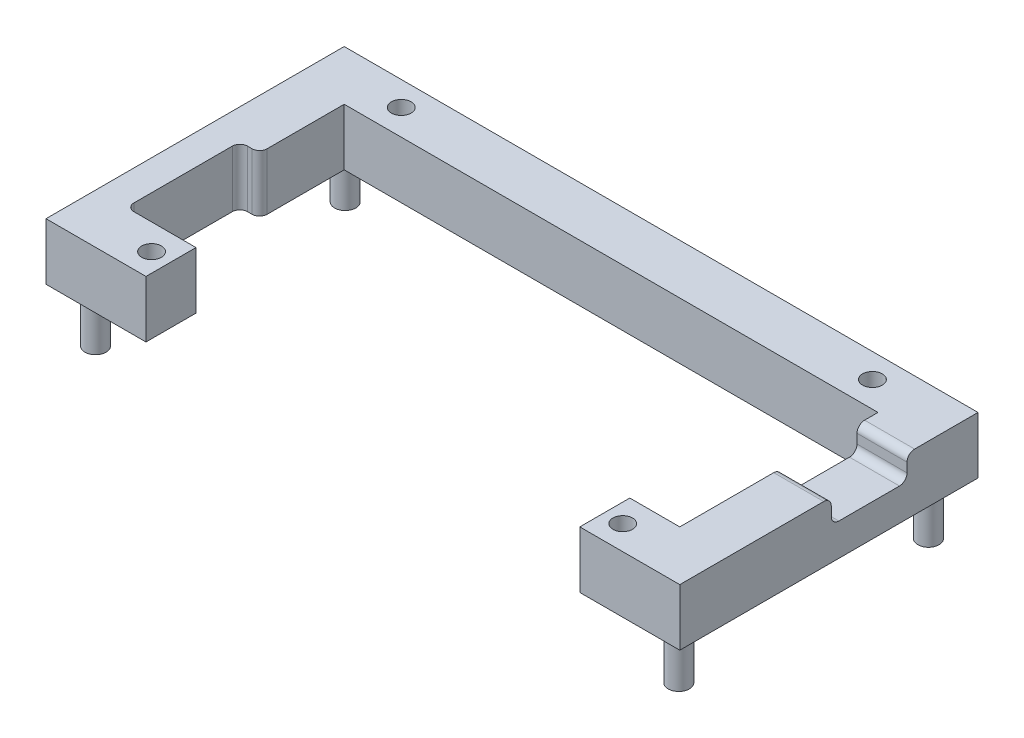
SolidWorks part; units mm, degrees
ref_plane "Front Plane" through (0, 0, 0) normal (0, 0, 1) x (1, 0, 0)
ref_plane "Top Plane" through (0, 0, 0) normal (0, 1, 0) x (1, 0, 0)
ref_plane "Right Plane" through (0, 0, 0) normal (1, 0, 0) x (0, 0, -1)
sketch "Sketch1" plane through (0, 0, 0) normal (0, 1, 0) x (1, 0, 0)
  line L0 (181.4198, 36.9979) -> (75.1552, 36.9979) construction
  line L1 (75.1552, 11.9979) -> (83.5372, 11.9979)
  line L2 (75.1552, 11.9979) -> (75.1552, 61.9979)
  line L3 (75.1552, 61.9979) -> (83.5372, 61.9979)
  line L4 (83.5372, 11.9979) -> (83.5372, 61.9979)
  line L5 (83.5372, 61.9979) -> (91.9192, 61.9979)
  line L6 (83.5372, 61.9979) -> (83.5372, 53.6159)
  line L7 (83.5372, 53.6159) -> (91.9192, 53.6159)
  line L8 (167.7876, 16.0648) -> (186.7138, 16.0648) construction
  line L9 (83.5372, 11.9979) -> (91.9192, 11.9979)
  line L10 (83.5372, 11.9979) -> (83.5372, 20.3799)
  line L11 (83.5372, 20.3799) -> (91.9192, 20.3799)
  line L12 (91.9192, 11.9979) -> (91.9192, 20.3799)
  line L13 (75.1552, 61.9979) -> (181.4198, 61.9979)
  line L17 (181.4198, 61.9979) -> (173.0378, 61.9979)
  line L18 (181.4198, 61.9979) -> (181.4198, 11.9979)
  line L19 (181.4198, 11.9979) -> (173.0378, 11.9979)
  line L20 (173.0378, 61.9979) -> (173.0378, 11.9979)
  line L21 (173.0378, 61.9979) -> (164.6558, 61.9979)
  line L22 (173.0378, 61.9979) -> (173.0378, 53.6159)
  line L23 (173.0378, 53.6159) -> (164.6558, 53.6159)
  line L25 (173.0378, 11.9979) -> (164.6558, 11.9979)
  line L26 (173.0378, 11.9979) -> (173.0378, 20.3799)
  line L27 (173.0378, 20.3799) -> (164.6558, 20.3799)
  line L28 (164.6558, 11.9979) -> (164.6558, 20.3799)
  line L29 (128.2875, 61.9979) -> (128.2875, -9.1774) construction
  line L30 (164.6558, 53.6159) -> (91.9192, 53.6159)
  circle A0 centre (167.7876, 57.931) radius 1.651
  circle A1 centre (167.7876, 16.0648) radius 1.651
  circle A2 centre (88.7875, 16.0648) radius 1.651
  circle A3 centre (88.7875, 57.931) radius 1.651
  point P32 (91.9192, 16.1889)
  point P34 (88.7875, 57.931)
  point P35 (88.7875, 16.0648)
  dimension "D15" = 3.302
  dimension "D16" = 3.1342
  dimension "D6" = 79.0001
  dimension "D1" = 8.382
  dimension "D3" = 50
  dimension "D4" = 8.382
  dimension "D5" = 50
  dimension "D7" = 8.382
  dimension "D8" = 8.382
  dimension "D9" = 8.382
  dimension "D10" = 8.382
  dimension "D11" = 8.382
  dimension "D12" = 8.382
  dimension "D13" = 8.382
  dimension "D14" = 8.382
  dimension "D17" = 3.1317
extrude "Boss-Extrude1" add sketch "Sketch1" along normal blind 9.525 contours L1 L4 L3 L2 | L13 L3 L5 | L13 L20 L19 L18 | L13 L23 L20 | L28 L25 L20 L27 | L9 L12 L11 L4 | L5 L4 L7 | L1 L4 L2 | L20 L19 L18 region at (79.3462, 0, -36.9979) region at (83.6557, 0, -16.1889) region at (128.2875, 0, -57.804) region at (177.2288, 0, -36.9979) region at (172.9193, 0, -16.1889)
sketch "Sketch2" plane through (181.4198, 0, 0) normal (1, 0, 0) x (0, 0, -1)
  line L0 (61.9979, 9.525) -> (11.9979, 9.525) construction
  line L1 (37.3979, 9.525) -> (50.0979, 9.525)
  line L2 (37.3979, 9.525) -> (37.3979, 5.4254)
  line L3 (37.3979, 5.4254) -> (50.0979, 5.4254)
  line L4 (50.0979, 9.525) -> (50.0979, 5.4254)
  line L5 (11.9979, 9.525) -> (11.9979, 0) construction
  dimension "D1" = 25.4
  dimension "D2" = 12.7
extrude "Cut-Extrude7" cut sketch "Sketch2" against normal blind 8.89 contours L2 L3 L4 L1
fillet "Fillet2" radius 1.27 4 edges at (177.2288, 5.4254, -37.3979) (177.2288, 9.525, -37.3979) (177.2288, 9.525, -50.0979) (177.2288, 5.4254, -50.0979)
sketch "Sketch3" plane through (0, 0, 0) normal (0, -1, 0) x (1, 0, 0)
  circle A0 centre (79.3895, -16.0648) radius 1.778
  circle A1 centre (177.1856, -16.0648) radius 1.778
  circle A2 centre (79.3895, -57.931) radius 1.778
  circle A3 centre (177.1856, -57.931) radius 1.778
extrude "Boss-Extrude3" add sketch "Sketch3" along normal blind 8.89 contours A0 | A2 | A3 | A1
sketch "Sketch4" plane through (0, 9.525, 0) normal (0, 1, 0) x (1, 0, 0)
  line L1 (83.5372, 20.3799) -> (80.2352, 20.3799)
  line L2 (83.5372, 20.3799) -> (83.5372, 39.4299)
  line L3 (83.5372, 39.4299) -> (80.2352, 39.4299)
  line L4 (80.2352, 20.3799) -> (80.2352, 39.4299)
  dimension "D1" = 3.302
  dimension "D2" = 19.05
extrude "Cut-Extrude8" cut sketch "Sketch4" against normal through all
fillet "Fillet3" radius 1.27 3 edges at (80.2352, 4.7625, -20.3799) (83.5372, 4.7625, -39.4299) (80.2352, 4.7625, -39.4299)
